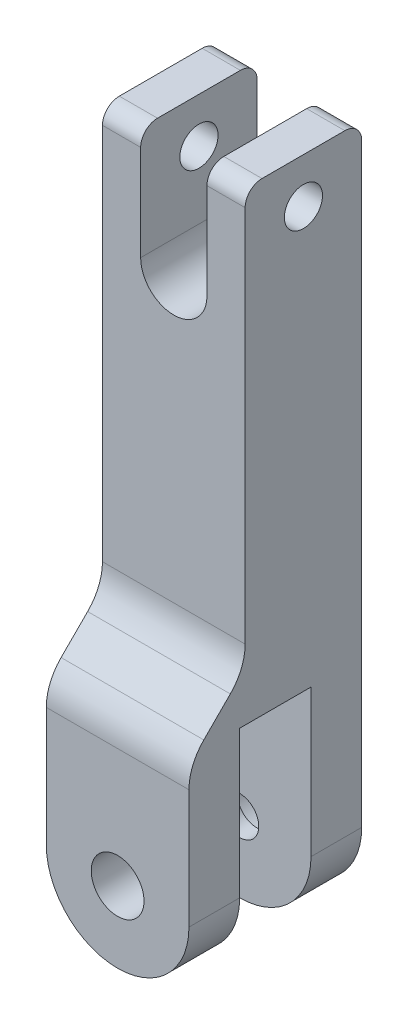
SolidWorks part; units mm, degrees
ref_plane "Front Plane" through (0, 0, 0) normal (0, 0, 1) x (1, 0, 0)
ref_plane "Top Plane" through (0, 0, 0) normal (0, 1, 0) x (1, 0, 0)
ref_plane "Right Plane" through (0, 0, 0) normal (1, 0, 0) x (0, 0, -1)
sketch "Sketch1" plane through (0, 0, 0) normal (0, 0, 1) x (1, 0, 0)
  line L6 (-6.35, 0) -> (-6.35, 54.45)
  line L7 (-6.35, 54.45) -> (6.35, 54.45)
  line L8 (6.35, 0) -> (6.35, 54.45)
  arc A0 (-6.35, 0) -> (6.35, 0) centre (0, 0) ccw
  dimension "D2" = 6.35
  dimension "D1" = 54.45
extrude "Boss-Extrude1" add sketch "Sketch1" along normal blind 15.375
sketch "Sketch2" plane through (6.35, 0, 0) normal (1, 0, 0) x (0, 0, -1)
  line L1 (-15.375, 54.45) -> (-10.375, 54.45)
  line L2 (-15.375, 54.45) -> (-15.375, 17.45)
  line L3 (-15.375, 17.45) -> (-10.375, 17.45)
  line L4 (-10.375, 54.45) -> (-10.375, 17.45)
  dimension "D1" = 5
  dimension "D2" = 37
extrude "Cut-Extrude1" cut sketch "Sketch2" against normal through all
sketch "Sketch3" plane through (6.35, 0, 0) normal (1, 0, 0) x (0, 0, -1)
  line L0 (-15.375, -6.35) -> (0, -6.35) construction
  line L1 (-4.5125, 4.18) -> (-10.8625, 4.18)
  line L2 (-4.5125, 4.18) -> (-4.5125, -6.35)
  line L3 (-4.5125, -6.35) -> (-10.8625, -6.35)
  line L4 (-10.8625, 4.18) -> (-10.8625, -6.35)
  line L5 (-15.375, 0) -> (0, 0) construction
  point P8 (-7.6875, 0)
  point P9 (-7.6875, 4.18)
  dimension "D1" = 6.35
  dimension "D2" = 10.53
extrude "Cut-Extrude2" cut sketch "Sketch3" against normal through all
sketch "Sketch4" plane through (0, 0, 0) normal (0, 0, -1) x (-1, 0, 0)
  line L0 (-6.35, 54.45) -> (6.35, 54.45) construction
  line L1 (-2.95, 54.45) -> (2.95, 54.45)
  line L2 (-2.95, 54.45) -> (-2.95, 44.45)
  line L4 (2.95, 54.45) -> (2.95, 44.45)
  arc A0 (-2.95, 44.45) -> (2.95, 44.45) centre (0, 44.45) ccw
  point P9 (0, 54.45)
  dimension "D2" = 2.95
  dimension "D1" = 10
extrude "Cut-Extrude3" cut sketch "Sketch4" against normal through all
sketch "Sketch5" plane through (0, 0, 15.375) normal (0, 0, 1) x (1, 0, 0)
  circle A0 centre (0, 0) radius 1.7
  circle A1 centre (0, 0) radius 2.35
  dimension "D1" = 3.4
  dimension "D2" = 4.7
extrude "Cut-Extrude4" cut sketch "Sketch5" against normal up to surface (4.5125 mm away) contours A0 region at (0, 0, 15.375) up to face at (0, 0.5025, 10.8625)
extrude "Cut-Extrude6" cut sketch "Sketch5<3>" against normal blind 4
sketch "Sketch5<3>" plane through (0, 0, 15.375) normal (0, 0, 1) x (1, 0, 0) same geometry as "Sketch5"
hole_wizard "CBORE for M3 SHCS1" positions "Sketch7" profile "Sketch8" counterbore size "M3" standard "ANSI Metric" end condition up to next
sketch "Sketch7" plane through (0, 0, 0) normal (0, 0, -1) x (-1, 0, 0)
  point P0 (0, 0)
sketch "Sketch8" plane through (0, 0, 0) normal (1, 0, 0) x (0, 1, 0)
  line L0 (0, 0) -> (0, 4.5125)
  line L1 (0, 4.5125) -> (1.7, 4.5125)
  line L3 (1.7, 4.5125) -> (1.7, 3)
  line L4 (1.7, 3) -> (3.25, 3)
  line L5 (3.25, 3) -> (3.25, 0)
  line L7 (3.25, 0) -> (0, 0)
  line L11 (0, -6.35) -> (0, 107.95) construction
  dimension "Thru Hole Dia." = 3.4
  dimension "Thru Hole Depth" = 4.5125
  dimension "C'Bore Dia." = 6.5
  dimension "C'Bore Depth" = 3
sketch "Sketch6" plane through (6.35, 0, 0) normal (1, 0, 0) x (0, 0, -1)
  line L0 (-10.375, 54.45) -> (0, 54.45) construction
  circle A0 centre (-5.1875, 50.45) radius 1.7
  point P5 (-5.1875, 54.45)
  dimension "D2" = 3.4
  dimension "D1" = 4
extrude "Cut-Extrude5" cut sketch "Sketch6" against normal through all
draft "Draft1" type of draft neutral plane draft angle 45 faces to draft 1 face at (0, 17.45, 12.875) neutral plane through (-6.35, 54.45, 10.375) neutral plane normal (0, 0, 1) parameters "D1"=45
draft "Draft2" type of draft neutral plane draft angle 35 faces to draft 1 face at (0, 4.18, 7.6875) neutral plane through (-6.35, 0, 15.375) neutral plane normal (-1, 0, 0) reverse direction yes parameters "D1"=35
fillet "Fillet1" radius 1.5 4 edges at (-4.65, 54.45, 10.375) (-4.65, 54.45, 0) (4.65, 54.45, 0) (4.65, 54.45, 10.375)
fillet "Fillet2" radius 4.5 2 edges at (0, 12.45, 15.375) (0, 17.45, 10.375)
